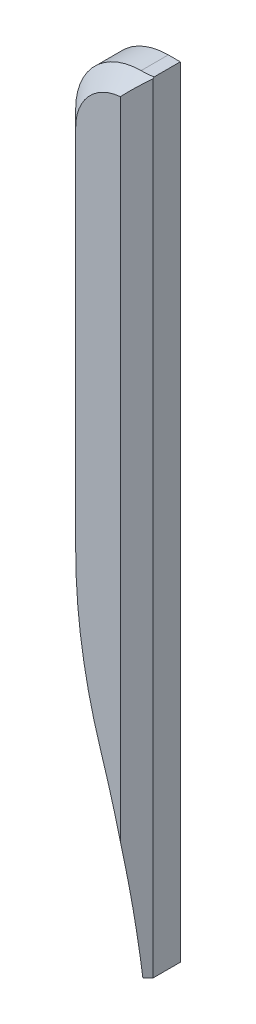
SolidWorks part; units mm, degrees
material "Сплав 2024"
ref_plane "Спереди" through (0, 0, 0) normal (0, 0, 1) x (1, 0, 0)
ref_plane "Сверху" through (0, 0, 0) normal (0, 1, 0) x (1, 0, 0)
ref_plane "Справа" through (0, 0, 0) normal (1, 0, 0) x (0, 0, -1)
sketch "Эскиз1" plane through (0, 0, 0) normal (0, 0, 1) x (1, 0, 0)
  line L0 (0, 0) -> (0, 85.2577)
  line L1 (-1.1, 85.2577) -> (0, 85.2577)
  line L2 (-7.1, 79.2577) -> (-7.1, 45.6025)
  arc A0 (-1.1, 85.2577) -> (-7.1, 79.2577) centre (-1.1, 79.2577) ccw
  arc A1 (-7.1, 45.6025) -> (-4.7333, 30.4017) centre (42.9, 45.6025) ccw
  arc A2 (0, 0) -> (-4.7333, 30.4017) centre (-100, 0) ccw
extrude "Бобышка-Вытянуть1" add sketch "Эскиз1" along normal blind 4
sketch "Эскиз2" plane through (0, 0, 4) normal (0, 0, 1) x (1, 0, 0)
  line L0 (-4.0336, 13.6707) -> (2.1328, 13.6707)
  line L1 (2.1328, 13.6707) -> (2.1328, -1.2962)
  line L2 (2.1328, -1.2962) -> (-4.0336, -1.2962)
  line L3 (-4.0336, -1.2962) -> (-4.0336, 13.6707)
extrude "Вырез-Вытянуть1" cut sketch "Эскиз2" against normal through all
chamfer "Фаска3" distance 1.5 angle 45 1 edges at (0, 49.4642, 4)
chamfer "Фаска4" distance 1.5 angle 45 4 edges at (-2.8939, 23.8833, 4) (-5.4818, 83.3565, 4) (-6.5048, 37.9105, 4) (-7.1, 62.4301, 4)
